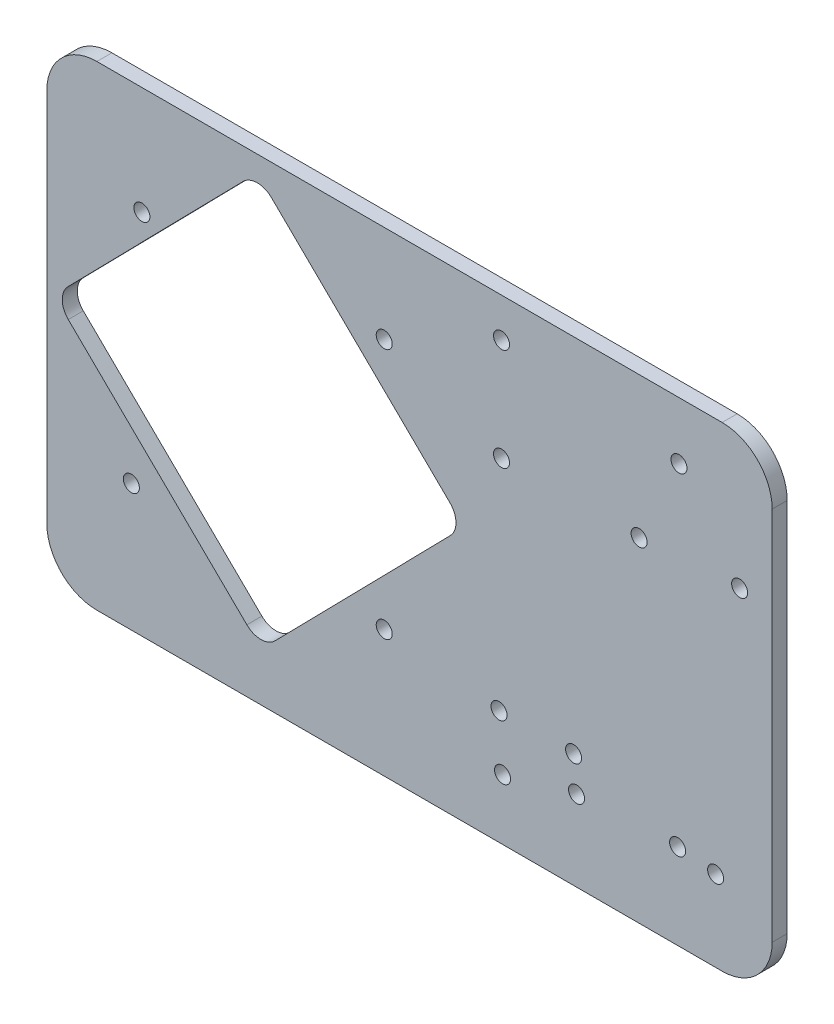
SolidWorks part; units mm, degrees
ref_plane "Plan de face" through (0, 0, 0) normal (0, 0, 1) x (1, 0, 0)
ref_plane "Plan de dessus" through (0, 0, 0) normal (0, 1, 0) x (1, 0, 0)
ref_plane "Plan de droite" through (0, 0, 0) normal (1, 0, 0) x (0, 0, -1)
sketch "Esquisse1" plane through (0, 0, 0) normal (0, 0, 1) x (1, 0, 0)
  line L0 (44.8821, 88.8903) -> (80.5904, 53.8914)
  line L1 (10, 0) -> (135, 0)
  line L2 (0, 10) -> (0, 85)
  line L3 (10, 95) -> (135, 95)
  line L4 (145, 10) -> (145, 85)
  line L5 (4.2835, 47.4686) -> (39.9918, 12.4698)
  line L6 (39.2256, 88.8335) -> (4.2268, 53.1252)
  line L7 (45.6484, 12.5266) -> (80.6472, 48.2349)
  line L8 (90.9, 87.2) -> (90.9, 66.7486) construction
  line L9 (90.9, 66.7486) -> (118.4, 66.7486) construction
  line L10 (90.4, 22.8) -> (105.3, 22.8) construction
  line L11 (67.45, 25.4) -> (16.9, 25.4) construction
  line L12 (67.45, 25.4) -> (67.45, 75.6) construction
  line L13 (3.0836, 50.2852) -> (84.2485, 51.0996) construction
  line L14 (42.0421, 90.0334) -> (42.8318, 11.3267) construction
  line L15 (59.4191, 42.7199) -> (51.0194, 34.1499) construction
  line L16 (59.4191, 42.7199) -> (42.9933, 58.8193) construction
  line L17 (51.0194, 34.1499) -> (34.5936, 50.2493) construction
  line L18 (42.9933, 58.8193) -> (34.5936, 50.2493) construction
  arc A0 (135, 95) -> (145, 85) centre (135, 85) cw
  arc A1 (135, 0) -> (145, 10) centre (135, 10) ccw
  arc A2 (10, 0) -> (0, 10) centre (10, 10) cw
  arc A3 (0, 85) -> (10, 95) centre (10, 85) cw
  arc A4 (4.2835, 47.4686) -> (4.2268, 53.1252) centre (7.0834, 50.3253) cw
  arc A5 (39.9918, 12.4698) -> (45.6484, 12.5266) centre (42.7917, 15.3265) ccw
  arc A6 (80.5904, 53.8914) -> (80.6472, 48.2349) centre (77.7905, 51.0348) cw
  arc A7 (44.8821, 88.8903) -> (39.2256, 88.8335) centre (42.0822, 86.0336) ccw
  circle A8 centre (90.9, 87.2) radius 1.6
  circle A9 centre (126.3689, 83.5358) radius 1.6
  circle A10 centre (138.5, 68.05) radius 1.6
  circle A11 centre (118.4, 66.7486) radius 1.6
  circle A12 centre (90.9, 66.7486) radius 1.6
  circle A13 centre (126.1, 17.1) radius 1.6
  circle A14 centre (133.7, 16.15) radius 1.6
  circle A15 centre (105.3, 22.8) radius 1.6
  circle A16 centre (90.4, 22.8) radius 1.6
  circle A17 centre (91.1, 12.1) radius 1.6
  circle A18 centre (105.9, 16.1) radius 1.6
  circle A19 centre (67.45, 25.4) radius 1.6
  circle A20 centre (19, 73.4) radius 1.6
  circle A21 centre (16.9, 25.4) radius 1.6
  circle A22 centre (67.45, 75.6) radius 1.6
  circle A23 centre (7.0834, 50.3253) radius 1.6 construction
  circle A24 centre (42.0822, 86.0336) radius 1.6 construction
  circle A25 centre (77.7905, 51.0348) radius 1.6 construction
  circle A26 centre (42.7917, 15.3265) radius 1.6 construction
  circle A27 centre (53.5119, 53.5506) radius 1.6 construction
  circle A28 centre (39.0011, 40.8886) radius 1.6 construction
  circle A29 centre (74.9623, 51.0064) radius 1.6 construction
  point P9 (145, 0)
  point P12 (0, 0)
  point P15 (0, 95)
  dimension "D3" = 10
  dimension "D11" = 4
  dimension "D12" = 3.2
  dimension "D15" = 3.2
  dimension "D18" = 3.2
  dimension "D20" = 25.35
  dimension "D21" = 3.2
  dimension "D24" = 3.2
  dimension "D25" = 3.2
  dimension "D30" = 3.2
  dimension "D33" = 3.2
  dimension "D36" = 3.2
  dimension "D39" = 3.2
  dimension "D42" = 3.2
  dimension "D43" = 3.2
  dimension "D47" = 3.2
  dimension "D49" = 3.2
  dimension "D50" = 20
  dimension "D52" = 3.2
  dimension "D53" = 3.2
  dimension "D54" = 3.2
  dimension "D55" = 3.2
  dimension "D56" = 3.2
  dimension "D60" = 4
  dimension "D62" = 4
  dimension "D66" = 3.2
  dimension "D77" = 3.2
  dimension "D80" = 3.2
  dimension "D1" = 145
  dimension "D2" = 95
  dimension "D4" = 58
  dimension "D5" = 44.425
  dimension "D6" = 44.425
  dimension "D7" = 36.8988
  dimension "D8" = 90
  dimension "D9" = 25.1883
  dimension "D10" = 58
  dimension "D13" = 52.5
  dimension "D14" = 6.2
  dimension "D16" = 17.0311
  dimension "D17" = 9.8642
  dimension "D19" = 4.9
  dimension "D22" = 25
  dimension "D23" = 26.6514
  dimension "D26" = 9.7
  dimension "D27" = 14.55
  dimension "D28" = 17.3
  dimension "D29" = 15.5
  dimension "D31" = 37.5
  dimension "D32" = 14.5
  dimension "D34" = 52.3
  dimension "D35" = 10.5
  dimension "D37" = 38.1
  dimension "D38" = 21.2
  dimension "D40" = 53
  dimension "D41" = 21.2
  dimension "D44" = 65.85
  dimension "D45" = 23.8
  dimension "D46" = 17.8
  dimension "D48" = 15.3
  dimension "D51" = 17.4
  dimension "D57" = 4
  dimension "D58" = 4
  dimension "D59" = 4
  dimension "D61" = 4
  dimension "D63" = 4
  dimension "D64" = 4
  dimension "D65" = 11.3
  dimension "D67" = 6
  dimension "D68" = 6
  dimension "D69" = 12
  dimension "D70" = 23
  dimension "D71" = 90
  dimension "D72" = 90
  dimension "D73" = 12
  dimension "D74" = 51.0194
  dimension "D75" = 21.5
  dimension "D76" = 2
  dimension "D78" = 23
  dimension "D79" = 2
base flange "Tôle de base pliée1" sketch "Esquisse1" thickness 3 reverse thickness direction no parameters "D1"=1.5
sketch "Lignes de pliage1" [suppressed] plane through (0, 0, 0) normal (0, 1, 0) x (1, 0, 0)
sketch "Cube de visualisation1" [suppressed] plane through (0, 0, 0) normal (0, 1, 0) x (1, 0, 0)
sheet metal parameters "Tôlerie1" thickness 3 parameters "D1"=1.5
flat pattern "Etat déplié1" [suppressed]
sketch "Lignes de pliage2" plane through (0, 0, 0) normal (0, 1, 0) x (1, 0, 0)
sketch3d "Cube de visualisation2" [suppressed]
  line L0 (-135, -85, 0) -> (10, -85, 0) construction
  line L1 (-135, 10, 0) -> (10, 10, 0) construction
  line L2 (-135, -85, 0) -> (-135, 10, 0) construction
  line L3 (10, -85, 0) -> (10, 10, 0) construction
